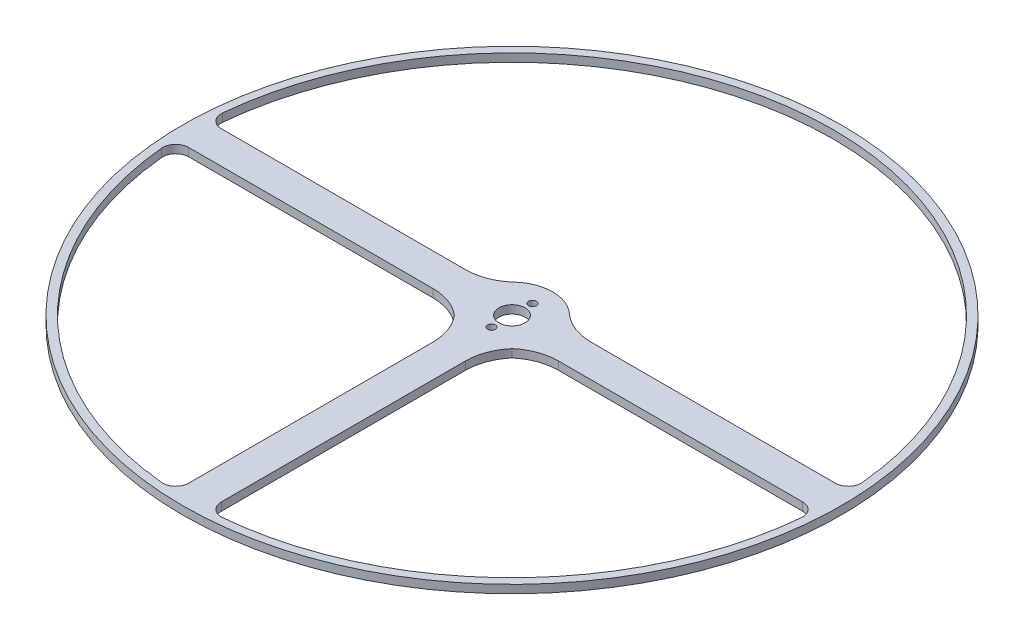
SolidWorks part; units mm, degrees
ref_plane "Front Plane" through (0, 0, 0) normal (0, 0, 1) x (1, 0, 0)
ref_plane "Top Plane" through (0, 0, 0) normal (0, 1, 0) x (1, 0, 0)
ref_plane "Right Plane" through (0, 0, 0) normal (1, 0, 0) x (0, 0, -1)
sketch "Sketch1" plane through (0, 0, 0) normal (0, 1, 0) x (1, 0, 0)
  line L0 (-14.5497, 6.35) -> (-125.2389, 6.35)
  line L1 (125.2389, -6.35) -> (14.5497, -6.35)
  line L3 (125.2389, 6.35) -> (14.5497, 6.35)
  line L12 (6.35, -14.5497) -> (6.35, -125.2389)
  line L13 (-6.35, -14.5497) -> (-6.35, -125.2389)
  line L14 (-14.5497, -6.35) -> (-125.2389, -6.35)
  arc A2 (14.5497, 6.35) -> (-14.5497, 6.35) centre (0, 0) ccw
  arc A3 (-14.5497, -6.35) -> (-6.35, -14.5497) centre (0, 0) ccw
  arc A4 (6.35, -14.5497) -> (14.5497, -6.35) centre (0, 0) ccw
  arc A5 (-125.2389, -6.35) -> (-6.35, -125.2389) centre (0, 0) ccw
  arc A6 (6.35, -125.2389) -> (125.2389, -6.35) centre (0, 0) ccw
  arc A7 (125.2389, 6.35) -> (-125.2389, 6.35) centre (0, 0) ccw
  point P0 (0, 0)
  dimension "D5" = 31.75
sketch "Screw holes" plane through (0, 0, 0) normal (0, 1, 0) x (1, 0, 0)
  circle A0 centre (0, 8) radius 1.5133
  circle A1 centre (0, -8) radius 1.5133
  circle A2 centre (0, 0) radius 5.08
  dimension "D1" = 16
  dimension "D3" = 3.0266
  dimension "D4" = 10.16
  dimension "D2" = 8
sketch "Sketch4" plane through (0, 0, 0) normal (0, 1, 0) x (1, 0, 0)
  circle A0 centre (0, 0) radius 128.5748
extrude "Boss-Extrude1" add sketch "Sketch4" along normal blind 3.175
extrude "Cut-Extrude2" cut sketch "Sketch1" along normal through all
extrude "middle holes" cut sketch "Screw holes" along normal through all
fillet "Filletmiddle" radius 20.32 6 edges at (14.5497, 1.5875, -6.35) (-14.5497, 1.5875, -6.35) (14.5497, 1.5875, 6.35) (6.35, 1.5875, 14.5497) (-14.5497, 1.5875, 6.35) (-6.35, 1.5875, 14.5497)
fillet "Filletsides" radius 5.08 6 edges at (125.2389, 1.5875, 6.35) (125.2389, 1.5875, -6.35) (-6.35, 1.5875, 125.2389) (6.35, 1.5875, 125.2389) (-125.2389, 1.5875, 6.35) (-125.2389, 1.5875, -6.35)
